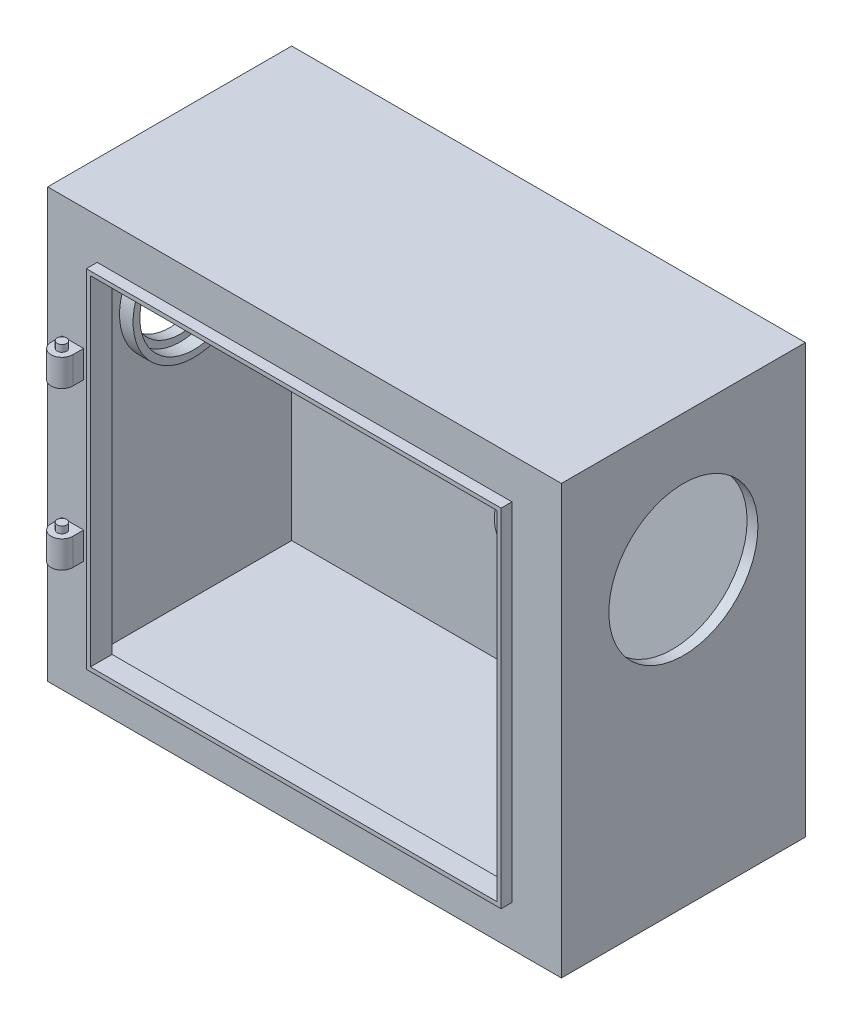
SolidWorks part; units mm, degrees
ref_plane "Alzado" through (0, 0, 0) normal (0, 0, 1) x (1, 0, 0)
ref_plane "Planta" through (0, 0, 0) normal (0, 1, 0) x (1, 0, 0)
ref_plane "Vista lateral" through (0, 0, 0) normal (1, 0, 0) x (0, 0, -1)
sketch "Croquis1" plane through (0, 0, 0) normal (0, 0, 1) x (1, 0, 0)
  line L0 (-189.5, 158) -> (189.5, 158)
  line L1 (-181.5, -150) -> (181.5, -150) construction
  line L2 (-181.5, -150) -> (-181.5, 150) construction
  line L3 (-181.5, 150) -> (181.5, 150) construction
  line L4 (181.5, -150) -> (181.5, 150) construction
  line L5 (-181.5, -150) -> (181.5, 150) construction
  line L6 (-181.5, 150) -> (181.5, -150) construction
  line L7 (189.5, -158) -> (189.5, 158)
  line L8 (-189.5, -158) -> (189.5, -158)
  line L9 (-189.5, -158) -> (-189.5, 158)
  point P0 (0, 0)
  dimension "D1" = 363
  dimension "D2" = 300
  dimension "D3" = 8
extrude "Saliente-Extruir1" add sketch "Croquis1" along normal blind 180
shell "Vaciado1" thickness 8 removed face at (0, 0, 180)
sketch "Croquis2" plane through (-189.5, 0, 0) normal (-1, 0, 0) x (0, 0, 1)
  line L0 (0, 158) -> (90, 158) construction
  line L1 (180, 158) -> (0, 158) construction
  circle A0 centre (90, 58) radius 35
extrude "Cortar-Extruir4" cut sketch "Croquis2" against normal blind 20 contours A0
sketch "Croquis4" plane through (-181.5, 0, 0) normal (1, 0, 0) x (0, 0, -1)
  circle A1 centre (-90, 58) radius 40
  circle A2 centre (-90, 58) radius 45
extrude "Saliente-Extruir4" add sketch "Croquis4" along normal blind 10
sketch "Croquis6" plane through (189.5, 0, 0) normal (1, 0, 0) x (0, 0, -1)
  line L0 (-90, 158) -> (-90, 58) construction
  line L1 (-180, 158) -> (0, 158) construction
  circle A0 centre (-90, 58) radius 55
extrude "Cortar-Extruir6" cut sketch "Croquis6" against normal blind 10 contours A0
sketch "Croquis7" plane through (0, 0, 8) normal (0, 0, 1) x (1, 0, 0)
  line L0 (0, 150) -> (0, -53) construction
  line L1 (181.5, 150) -> (-181.5, 150) construction
  circle A0 centre (0, -53) radius 24
  circle A2 centre (0, -53) radius 21
  dimension "D1" = 42
extrude "Saliente-Extruir9" add sketch "Croquis7" along normal blind 8
ref_plane "Plano6" through (0, 0, 180) normal (0, 0, 1) x (1, 0, 0)
sketch "Croquis11" plane through (0, 0, 180) normal (0, 0, 1) x (1, 0, 0)
  line L1 (181.5, 150) -> (-181.5, 150)
  line L2 (181.5, 150) -> (181.5, -150)
  line L3 (181.5, -150) -> (-181.5, -150)
  line L4 (-181.5, 150) -> (-181.5, -150)
  line L5 (181.5, 150) -> (-181.5, -150) construction
  line L6 (181.5, -150) -> (-181.5, 150) construction
  line L7 (-150, 125) -> (150, 125)
  line L8 (-150, 125) -> (-150, -125)
  line L9 (-150, -125) -> (150, -125)
  line L10 (150, 125) -> (150, -125)
  line L11 (-150, 125) -> (150, -125) construction
  line L12 (-150, -125) -> (150, 125) construction
  point P0 (0, 0)
  point P7 (0, 0)
  dimension "D1" = 300
  dimension "D2" = 250
extrude "Saliente-Extruir10" add sketch "Croquis11" against normal blind 8
sketch "Croquis12" plane through (0, 0, 180) normal (0, 0, 1) x (1, 0, 0)
  line L1 (150, -125) -> (-150, -125)
  line L2 (150, -125) -> (150, 125)
  line L3 (150, 125) -> (-150, 125)
  line L4 (-150, -125) -> (-150, 125)
  line L5 (150, -125) -> (-150, 125) construction
  line L6 (150, 125) -> (-150, -125) construction
  line L7 (153, -128) -> (-153, -128)
  line L8 (153, -128) -> (153, 128)
  line L9 (153, 128) -> (-153, 128)
  line L10 (-153, -128) -> (-153, 128)
  line L11 (153, -128) -> (-153, 128) construction
  line L12 (153, 128) -> (-153, -128) construction
  point P0 (0, 0)
  point P8 (0, 0)
  dimension "D1" = 3
  dimension "D2" = 3
extrude "Saliente-Extruir11" add sketch "Croquis12" along normal blind 8
sketch "Croquis13" plane through (0, 0, 180) normal (0, 0, 1) x (1, 0, 0)
  line L0 (189.5, 158) -> (-189.5, 158) construction
  line L1 (-179, 68) -> (-163, 68)
  line L2 (-179, 68) -> (-179, 48)
  line L3 (-179, 48) -> (-163, 48)
  line L4 (-163, 68) -> (-163, 48)
  line L5 (-179, 68) -> (-163, 48) construction
  line L6 (-179, 48) -> (-163, 68) construction
  line L7 (-153, 128) -> (-153, -128) construction
  point P0 (-171, 58)
  dimension "D1" = 100
  dimension "D2" = 20
  dimension "D3" = 16
  dimension "D4" = 10
extrude "Saliente-Extruir13" add sketch "Croquis13" along normal blind 8
sketch "Croquis14" plane through (0, 68, 0) normal (0, 1, 0) x (1, 0, 0)
  line L0 (-163, -188) -> (-179, -188) construction
  line L1 (-179, -188) -> (-163, -188)
  arc A0 (-179, -188) -> (-163, -188) centre (-171, -188) ccw
extrude "Saliente-Extruir14" add sketch "Croquis14" against normal blind 20
sketch "Croquis15" plane through (0, 68, 0) normal (0, 1, 0) x (1, 0, 0)
  circle A0 centre (-171, -188) radius 3.5
  arc A1 (-179, -188) -> (-163, -188) centre (-171, -188) ccw construction
  dimension "D1" = 7
extrude "Saliente-Extruir15" add sketch "Croquis15" along normal blind 5
sketch "Croquis17" plane through (0, 0, 180) normal (0, 0, 1) x (1, 0, 0)
  line L1 (-153, 128) -> (-153, -128) construction
  line L2 (-179, -48) -> (-163, -48)
  line L3 (-179, -48) -> (-179, -68)
  line L4 (-179, -68) -> (-163, -68)
  line L5 (-163, -48) -> (-163, -68)
  line L6 (-179, -48) -> (-163, -68) construction
  line L7 (-179, -68) -> (-163, -48) construction
  line L8 (-189.5, -158) -> (189.5, -158) construction
  point P2 (-171, -58)
  dimension "D1" = 20
  dimension "D2" = 16
  dimension "D3" = 10
  dimension "D4" = 100
extrude "Saliente-Extruir16" add sketch "Croquis17" along normal blind 8
sketch "Croquis18" plane through (0, -48, 0) normal (0, 1, 0) x (1, 0, 0)
  line L0 (-179, -188) -> (-163, -188)
  arc A0 (-179, -188) -> (-163, -188) centre (-171, -188) ccw
extrude "Saliente-Extruir17" add sketch "Croquis18" against normal blind 20
sketch "Croquis19" plane through (0, -48, 0) normal (0, 1, 0) x (1, 0, 0)
  circle A0 centre (-171, -188) radius 3.5
  arc A1 (-179, -188) -> (-163, -188) centre (-171, -188) ccw construction
  dimension "D1" = 7
extrude "Saliente-Extruir18" add sketch "Croquis19" along normal blind 5
